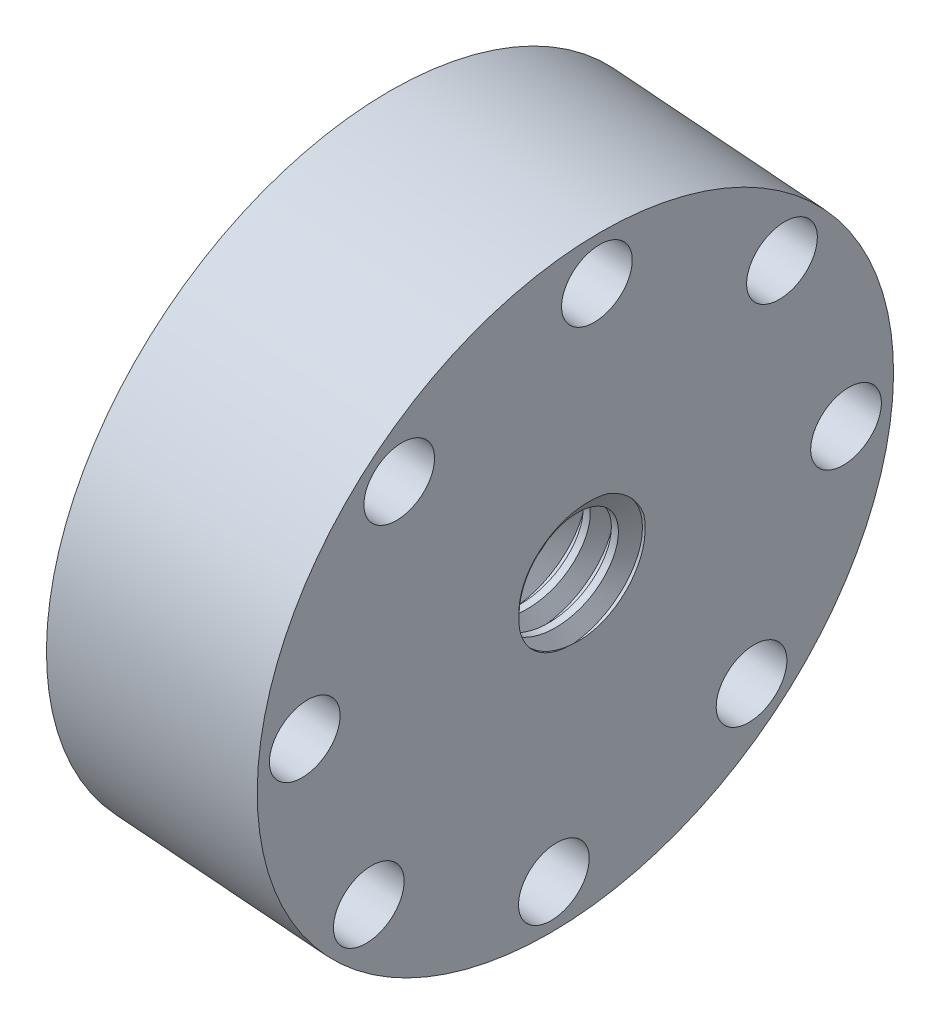
SolidWorks part; units mm, degrees
ref_plane "Front Plane" through (0, 0, 0) normal (0, 0, 1) x (1, 0, 0)
ref_plane "Top Plane" through (0, 0, 0) normal (0, 1, 0) x (1, 0, 0)
ref_plane "Right Plane" through (0, 0, 0) normal (1, 0, 0) x (0, 0, -1)
sketch "Sketch1" plane through (234.2789, -18.689, 0) normal (0.9968, -0.0795, 0) x (0, 0, -1)
  circle A1 centre (-43.1743, 8.5503) radius 14.2875
  dimension "D1" = 28.575
extrude "Boss-Extrude1" add sketch "Sketch1" against normal blind 9.525
sketch "Sketch2" plane through (234.2789, -18.689, 0) normal (0.9968, -0.0795, 0) x (0, 0, -1)
  circle A0 centre (-43.1743, 8.5503) radius 2.54
  dimension "D1" = 5.08
extrude "Cut-Extrude1" cut sketch "Sketch2" against normal blind 6.35
sketch "Sketch3" plane through (224.784, -17.9316, 0) normal (-0.9968, 0.0795, 0) x (0, 0, 1)
  circle A0 centre (43.1743, 20.7423) radius 1.5875
  circle A1 centre (43.1743, 8.5503) radius 14.2875 construction
  circle A2 centre (43.1743, 8.5503) radius 14.2875
  circle A3 centre (51.7953, 17.1714) radius 1.5875
  circle A4 centre (55.3663, 8.5503) radius 1.5875
  circle A5 centre (51.7953, -0.0707) radius 1.5875
  circle A6 centre (43.1743, -3.6417) radius 1.5875
  circle A7 centre (34.5532, -0.0707) radius 1.5875
  circle A8 centre (30.9823, 8.5503) radius 1.5875
  circle A9 centre (34.5532, 17.1714) radius 1.5875
  point P21 (43.1743, 8.5503)
  dimension "D1" = 3.175
  dimension "D3" = 12.192
  dimension "D2" = 8
extrude "Cut-Extrude2" cut sketch "Sketch3" against normal blind 10 contours A8 | A0 | A3 | A4 | A5 | A6 | A7 | A9 region at (226.4335, 2.7451, 43.1743) region at (226.1495, -0.8146, 51.7953) region at (225.464, -9.4083, 55.3663) region at (224.7784, -18.0021, 51.7953) region at (224.4945, -21.5617, 43.1743) region at (224.7784, -18.0021, 34.5532) region at (225.464, -9.4083, 30.9823)
sketch "Sketch4" plane through (234.2789, -18.689, 0) normal (0.9968, -0.0795, 0) x (0, 0, -1)
  line L0 (-57.4618, 8.5503) -> (-28.8868, 8.5503) construction
  circle A0 centre (-43.1743, 8.5503) radius 14.2875 construction
thread "Thread1" pitch 1.27 method cut profile "Thread Profile1" start angle 0, offset 0.9525, length 6.35, pitch 1.27, diameter 5.08
ref_plane "Plane1" through (235.9083, -10.2415, 45.7143) normal (-0.0795, -0.9968, 0) x (0, 0, 1)
sketch "Thread Profile1" plane through (235.9083, -10.2415, 45.7143) normal (-0.0795, -0.9968, 0) x (0, 0, 1)
  line L0 (0, 0) -> (0, 1.27) construction
  line L1 (0, 0) -> (0.6874, 0.3969)
  line L2 (0.6874, 0.3969) -> (0.6874, 0.5556)
  line L3 (0.6874, 0.5556) -> (0, 0.9525)
  line L4 (0.6874, 0.4762) -> (0, 0.4762) construction
  line L11 (0, 0) -> (0, 0.9525)
  point P2 (0, 0)
  dimension "Pitch" = 1.27
  dimension "Profile_Angle" = 60
  dimension "Profile_Land" = 0.1588
  dimension "Profile_Height" = 0.6874
